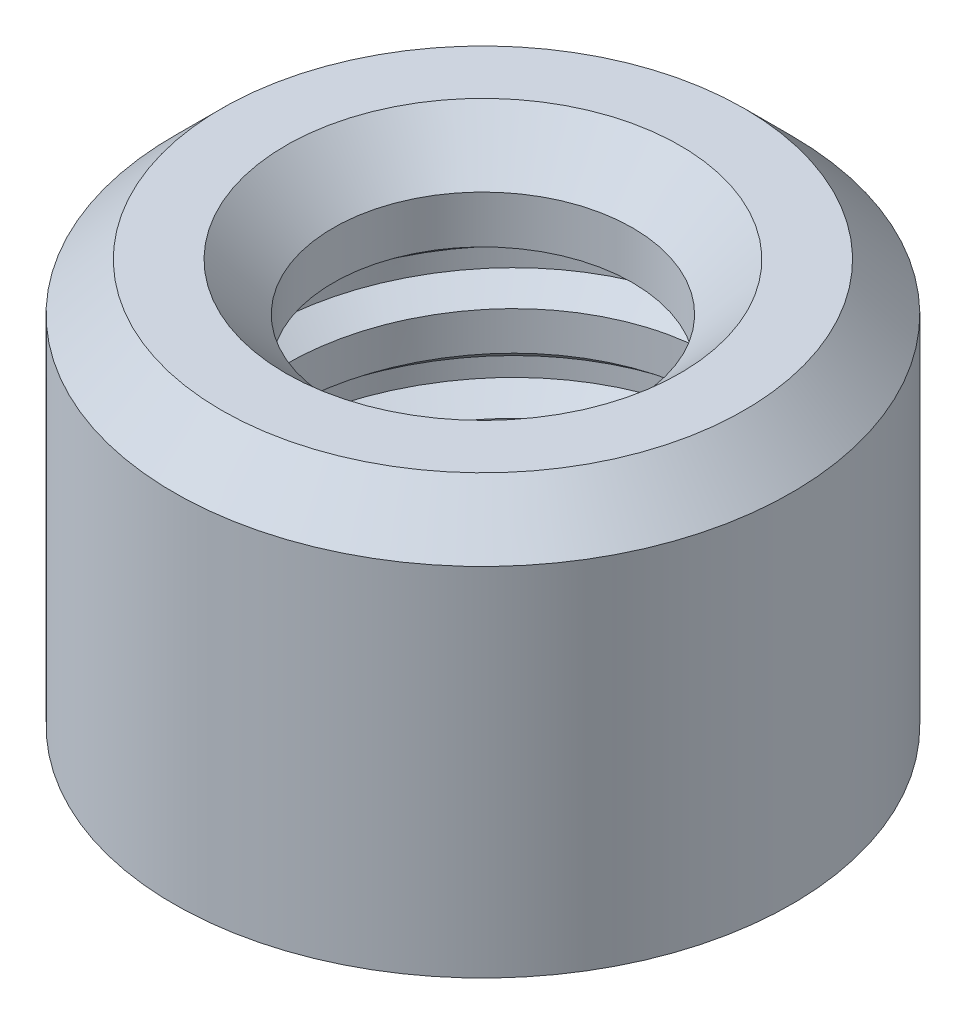
SolidWorks part; units mm, degrees
ref_plane "Front Plane" through (0, 0, 0) normal (0, 0, 1) x (1, 0, 0)
ref_plane "Top Plane" through (0, 0, 0) normal (0, 1, 0) x (1, 0, 0)
ref_plane "Right Plane" through (0, 0, 0) normal (1, 0, 0) x (0, 0, -1)
sketch "Sketch1" plane through (0, 0, 0) normal (0, 1, 0) x (1, 0, 0)
  circle A0 centre (0, 0) radius 4.5
  circle A1 centre (0, 0) radius 6.5
  dimension "D1" = 9
  dimension "D2" = 2
extrude "Boss-Extrude1" add sketch "Sketch1" along normal blind 6.5
sketch "Sketch2" plane through (0, 6.5, 0) normal (0, 1, 0) x (1, 0, 0)
  circle A1 centre (0, 0) radius 3.15
  circle A3 centre (0, 0) radius 6.5
  circle A4 centre (0, 0) radius 6.5
  dimension "D1" = 6.3
  dimension "D2" = 0
extrude "Boss-Extrude2" add sketch "Sketch2" along normal blind 2
chamfer "Chamfer1" distance 1 angle 45 1 edges at (0, 8.5, 3.15)
sketch "Sketch3" plane through (0, 6.5, 0) normal (0, -1, 0) x (1, 0, 0)
  circle A0 centre (0, 0) radius 4.5
  circle A1 centre (0, 0) radius 4.5 construction
curve "Helix/Spiral1" pitch 2 height 8 radius 4.5 left hand yes centre (0, 6.5, 0) axis (0, -1, 0) start towards (0, 0, -1)
ref_plane "Plane1" through (-3.182, 6.5, 3.182) normal (0.7053, -0.0706, 0.7053) x (0.7088, 0.0632, -0.7025)
sketch "Sketch4" plane through (-3.182, 6.5, 3.182) normal (0.7053, -0.0706, 0.7053) x (0.7088, 0.0632, -0.7025)
  line L0 (0.5784, 0.9637) -> (0.4389, -1.0314)
  line L1 (0.4389, -1.0314) -> (-0.5029, -0.1636)
  line L2 (-0.5029, -0.1636) -> (-0.475, 0.2354)
  line L3 (-0.475, 0.2354) -> (0.5784, 0.9637)
  line L4 (-0.4889, 0.0359) -> (0.5086, -0.0339) construction
  line L5 (0.406, 0.7048) -> (0.406, -0.8068) construction
  dimension "D1" = 0.4
  dimension "D2" = 2
  dimension "D3" = 1
  dimension "D4" = 4
sweep "Cut-Sweep1" cut profiles "Sketch4" path "Helix/Spiral1" align with end faces yes
chamfer "Chamfer2" distance 1 angle 45 1 edges at (0, 8.5, 6.5)
